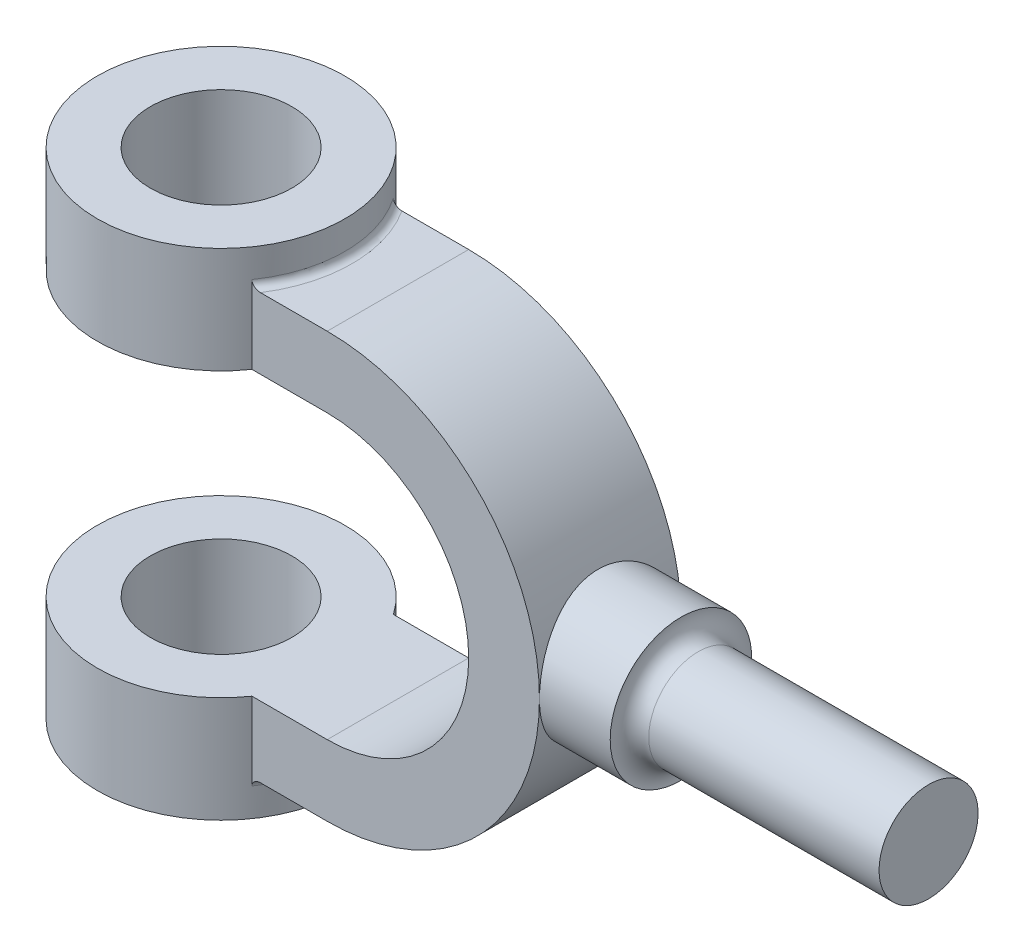
SolidWorks part; units mm, degrees
note: The reader was unsure of these and kept them because the rebuilt part matched: shared geometry of "Sketch1<4>".
ref_plane "Front Plane" through (0, 0, 0) normal (0, 0, 1) x (1, 0, 0)
ref_plane "Top Plane" through (0, 0, 0) normal (0, 1, 0) x (1, 0, 0)
ref_plane "Right Plane" through (0, 0, 0) normal (1, 0, 0) x (0, 0, -1)
sketch "Sketch1" plane through (0, 0, 0) normal (0, 0, 1) x (1, 0, 0)
  line L0 (-93.3028, 0) -> (268.7526, 0) construction
  line L1 (0, 84.3438) -> (0, -84.3438) construction
  line L2 (0, 60) -> (-21.3, 60)
  line L3 (-21.3, 60) -> (-21.3, 40)
  line L4 (-21.3, 40) -> (0, 40)
  line L5 (-21.3, -40) -> (0, -40)
  line L6 (-21.3, -60) -> (-21.3, -40)
  line L7 (0, -60) -> (-21.3, -60)
  line L8 (56.5685, 20) -> (80, 20)
  line L9 (84.899, 14) -> (150, 14)
  line L10 (150, 14) -> (150, 0)
  line L11 (60, 0) -> (150, 0)
  arc A0 (0, 40) -> (0, -40) centre (0, 0) cw
  arc A1 (0, 60) -> (0, -60) centre (0, 0) cw
  arc A2 (80, 20) -> (84.899, 14) centre (84.899, 19) ccw
  point P6 (0, 0)
  dimension "D1" = 40
  dimension "D4" = 5
  dimension "D3" = 21.3
  dimension "D5" = 14
  dimension "D6" = 20
  dimension "D7" = 70
  dimension "D8" = 80
  dimension "D2" = 20
revolve "Revolve-Thin1" add sketch "Sketch1" angle 360 about L0
extrude "Boss-Extrude1" add sketch "Sketch1<4>" along normal mid plane 40 contours L4 A0 L5 L6 L7 A1 L2 L3
sketch "Sketch1<4>" plane through (0, 0, 0) normal (0, 0, 1) x (1, 0, 0) same geometry as "Sketch1"
ref_plane "Plane1" through (0, 40, 0) normal (0, -1, 0) x (-1, 0, 0)
sketch "Sketch2" plane through (0, 40, 0) normal (0, 1, 0) x (1, 0, 0)
  line L0 (158.9815, 0) -> (-113.217, 0) construction
  line L1 (-50, 62.9846) -> (-50, -62.9846) construction
  line L2 (0, -20) -> (0, 20) construction
  circle A0 centre (-50, 0) radius 20
  circle A1 centre (-50, 0) radius 35
  point P6 (-50, 0)
  dimension "D2" = 40
  dimension "D3" = 70
  dimension "D1" = 50
extrude "Boss-Extrude2" add sketch "Sketch2" along normal blind 30
fillet "Fillet1" radius 2 1 edges at (-15, 60, 0)
mirror "Mirror3" about plane through (0, 0, 0) normal (0, 1, 0) of "Boss-Extrude2"
fillet "Fillet2" radius 2 1 edges at (-15, -60, 0)
